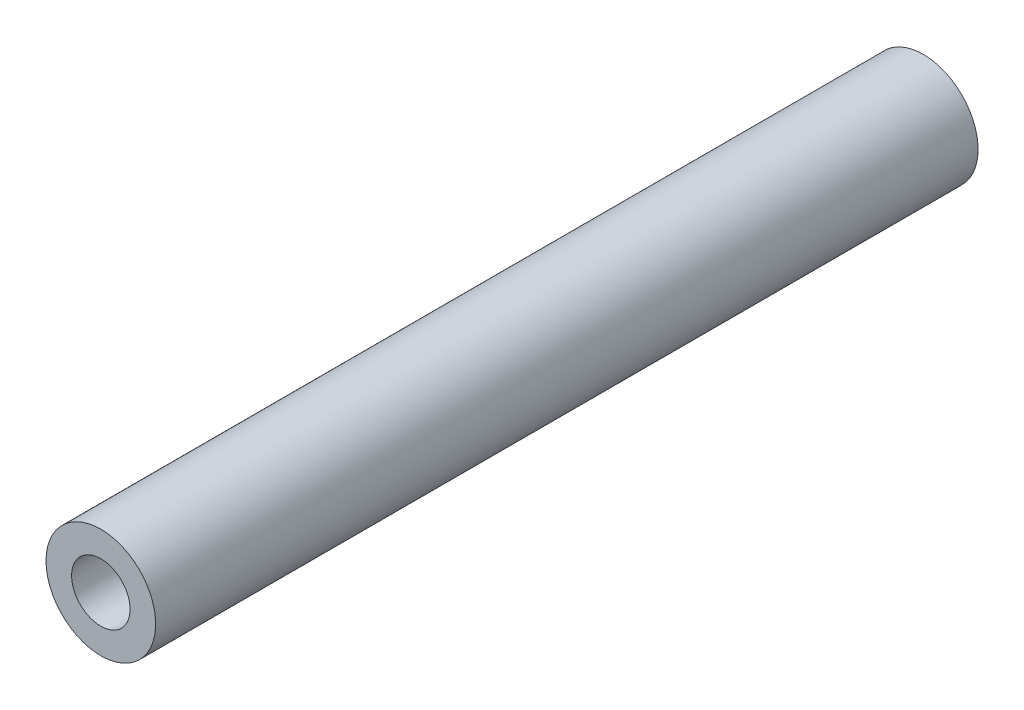
SolidWorks part; units mm, degrees
ref_plane "Front Plane" through (0, 0, 0) normal (0, 0, 1) x (1, 0, 0)
ref_plane "Top Plane" through (0, 0, 0) normal (0, 1, 0) x (1, 0, 0)
ref_plane "Right Plane" through (0, 0, 0) normal (1, 0, 0) x (0, 0, -1)
sketch "Sketch3" plane through (0, 0, 0) normal (0, 0, 1) x (1, 0, 0)
  circle A0 centre (0, 0) radius 1.6 construction
  circle A1 centre (0, 0) radius 3 construction
  point P6 (0, -1.6)
  dimension "OD" = 6
  dimension "ID" = 3.2
sketch "Sketch1" plane through (0, 0, 0) normal (1, 0, 0) x (0, 0, -1)
  line L0 (-22.5, -1.6) -> (-22.5, 1.6) construction
  line L1 (22.5, -3) -> (-22.5, -3) construction
  line L2 (22.5, -3) -> (22.5, 3) construction
  line L3 (22.5, 3) -> (-22.5, 3) construction
  line L4 (-22.5, -3) -> (-22.5, 3) construction
  line L5 (0, 3) -> (0, -3) construction
  line L6 (22.5, 0) -> (-22.5, 0) construction
  point P0 (0, 0)
  point P7 (-22.5, 0)
  dimension "OD" = 6
  dimension "ID" = 3.2
sketch "Sketch2" plane through (0, 0, 0) normal (0, 0, 1) x (1, 0, 0)
  circle A0 centre (0, 0) radius 3
  circle A1 centre (0, 0) radius 1.6
extrude "Extrude1" add sketch "Sketch2" along normal up to vertex and the other way up to vertex up to point (0, -3, 22.5) other way up to point (0, 3, -22.5)
equation "\"ID@Sketch1\" = \"ID@Sketch3\""
equation "\"OD@Sketch1\" = \"OD@Sketch3\""
